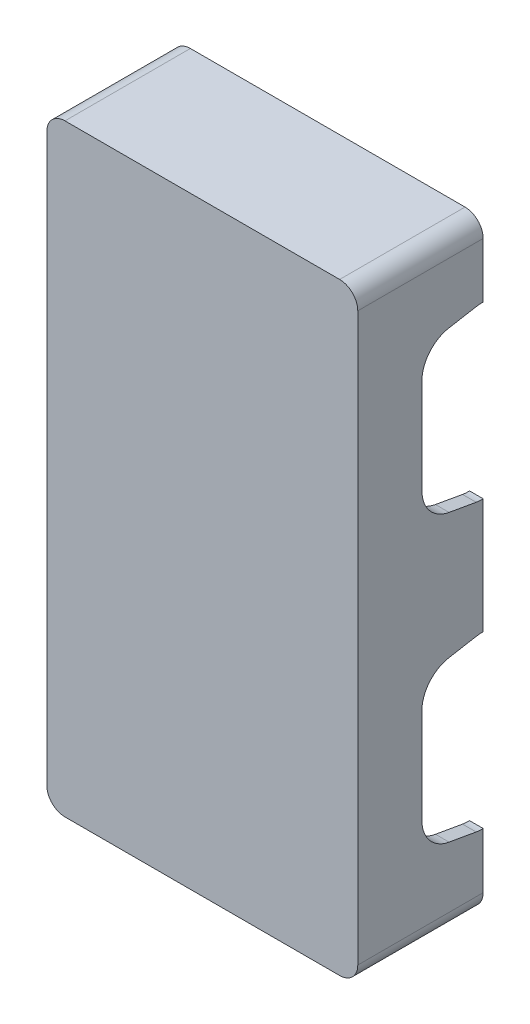
SolidWorks part; units mm, degrees
ref_plane "Front Plane" through (0, 0, 0) normal (0, 0, 1) x (1, 0, 0)
ref_plane "Top Plane" through (0, 0, 0) normal (0, 1, 0) x (1, 0, 0)
ref_plane "Right Plane" through (0, 0, 0) normal (1, 0, 0) x (0, 0, -1)
sketch "Sketch1" plane through (0, 0, 0) normal (0, 0, 1) x (1, 0, 0)
  line L0 (-32.3, 64.5) -> (2, 64.5)
  line L1 (-30.3, 62.5) -> (0, 62.5) construction
  line L2 (-30.3, 62.5) -> (-30.3, 0) construction
  line L3 (-30.3, 0) -> (0, 0) construction
  line L4 (0, 62.5) -> (0, 0) construction
  line L5 (2, 64.5) -> (2, -2)
  line L6 (-32.3, -2) -> (2, -2)
  line L7 (-32.3, 64.5) -> (-32.3, -2)
  dimension "D1" = 2
extrude "Boss-Extrude3" add sketch "Sketch1" along normal offset from surface 1.5 and the other way offset from surface (16.5814 mm away) 1.5
sketch "Sketch3" plane through (-32.3, 0, 0) normal (-1, 0, 0) x (0, 0, 1)
  line L0 (-13.4464, 47.86) -> (-13.4464, 14.26) construction
  line L1 (-9.7847, 11.1874) -> (-6.7947, 11.7146) construction
  line L2 (-4.2164, 14.7872) -> (-4.2164, 47.3328) construction
  line L3 (-6.7947, 50.4054) -> (-9.7847, 50.9326) construction
  line L5 (-13.9464, 47.86) -> (-13.9464, 14.26)
  line L6 (-9.6978, 10.695) -> (-6.7078, 11.2222)
  line L12 (-13.4464, 47.86) -> (-13.4464, 14.26) construction
  line L13 (-9.7847, 11.1874) -> (-6.7947, 11.7146) construction
  line L14 (-4.2164, 14.7872) -> (-4.2164, 47.3328) construction
  line L15 (-6.7947, 50.4054) -> (-9.7847, 50.9326) construction
  line L16 (-3.7164, 14.7872) -> (-3.7164, 47.3328)
  line L17 (-6.7078, 50.8978) -> (-9.6978, 51.425)
  spline S0 degree 3 poles (-13.4464, 14.26) (-13.4464, 12.1686) (-11.8443, 10.8242) (-9.7847, 11.1874) knots 0 0 0 0 1 1 1 1 weights 1 0.761858 0.761858 1 construction
  spline S1 degree 3 poles (-6.7947, 11.7146) (-5.2347, 11.9897) (-4.2164, 13.2032) (-4.2164, 14.7872) knots 0 0 0 0 1 1 1 1 weights 1 0.84403 0.84403 1 construction
  spline S2 degree 3 poles (-4.2164, 47.3328) (-4.2164, 48.9169) (-5.2347, 50.1303) (-6.7947, 50.4054) knots 0 0 0 0 1 1 1 1 weights 1 0.84403 0.84403 1 construction
  spline S3 degree 3 poles (-9.7847, 50.9326) (-11.8443, 51.2958) (-13.4464, 49.9514) (-13.4464, 47.86) knots 0 0 0 0 1 1 1 1 weights 1 0.761858 0.761858 1 construction
  spline S4 degree 3 poles (-13.4464, 14.26) (-13.4464, 12.1686) (-11.8443, 10.8242) (-9.7847, 11.1874) knots 0 0 0 0 1 1 1 1 weights 1 0.761858 0.761858 1 construction
  spline S5 degree 3 poles (-6.7947, 11.7146) (-5.2347, 11.9897) (-4.2164, 13.2032) (-4.2164, 14.7872) knots 0 0 0 0 1 1 1 1 weights 1 0.84403 0.84403 1 construction
  spline S6 degree 3 poles (-4.2164, 47.3328) (-4.2164, 48.9169) (-5.2347, 50.1303) (-6.7947, 50.4054) knots 0 0 0 0 1 1 1 1 weights 1 0.84403 0.84403 1 construction
  spline S7 degree 3 poles (-9.7847, 50.9326) (-11.8443, 51.2958) (-13.4464, 49.9514) (-13.4464, 47.86) knots 0 0 0 0 1 1 1 1 weights 1 0.761858 0.761858 1 construction
  spline S8 degree 1 poles (-13.9464, 14.26) (-9.6978, 10.695) knots 0 0 1 1 construction
  spline S9 degree 1 poles (-6.7078, 11.2222) (-3.7164, 14.7872) knots 0 0 1 1 construction
  spline S10 degree 1 poles (-3.7164, 47.3328) (-6.7078, 50.8978) knots 0 0 1 1 construction
  spline S11 degree 1 poles (-9.6978, 51.425) (-13.9464, 47.86) knots 0 0 1 1 construction
  spline S12 degree 3 poles (-13.9464, 14.26) (-13.9464, 14.0193) (-13.9017, 13.5499) (-13.5942, 12.5442) (-12.7412, 11.3822) (-11.4487, 10.7439) (-10.4049, 10.6158) (-9.9349, 10.6532) (-9.6978, 10.695) knots 0 0 0 0 0.125 0.25 0.5 0.75 0.875 1 1 1 1
  spline S13 degree 3 poles (-6.7078, 11.2222) (-6.308, 11.2927) (-5.5445, 11.5574) (-4.4978, 12.4053) (-3.8445, 13.5834) (-3.7164, 14.3812) (-3.7164, 14.7872) knots 0 0 0 0 0.25 0.5 0.75 1 1 1 1
  spline S14 degree 3 poles (-3.7164, 47.3328) (-3.7164, 47.7388) (-3.8445, 48.5366) (-4.4978, 49.7147) (-5.5445, 50.5626) (-6.308, 50.8273) (-6.7078, 50.8978) knots 0 0 0 0 0.25 0.5 0.75 1 1 1 1
  spline S15 degree 3 poles (-9.6978, 51.425) (-9.9349, 51.4668) (-10.4049, 51.5042) (-11.4487, 51.3761) (-12.7412, 50.7379) (-13.5942, 49.5758) (-13.9017, 48.5701) (-13.9464, 48.1007) (-13.9464, 47.86) knots 0 0 0 0 0.125 0.25 0.5 0.75 0.875 1 1 1 1
  dimension "D1" = 0.5
extrude "Cut-Extrude1" cut sketch "Sketch3" against normal blind 5
sketch "Sketch4" plane through (2, 0, 0) normal (1, 0, 0) x (0, 0, -1)
  line L0 (6.9047, 38.7046) -> (9.8947, 38.1774) construction
  line L1 (4.3264, 52.2728) -> (4.3264, 41.7772) construction
  line L2 (13.5564, 41.25) -> (13.5564, 52.8) construction
  line L3 (9.8947, 55.8726) -> (6.9047, 55.3454) construction
  line L4 (6.9047, 38.7046) -> (9.8947, 38.1774) construction
  line L5 (4.3264, 52.2728) -> (4.3264, 41.7772) construction
  line L6 (13.5564, 41.25) -> (13.5564, 52.8) construction
  line L7 (9.8947, 55.8726) -> (6.9047, 55.3454) construction
  line L8 (4.3264, 20.7728) -> (4.3264, 10.2772) construction
  line L9 (6.9047, 7.2046) -> (9.8947, 6.6774) construction
  line L10 (13.5564, 9.75) -> (13.5564, 21.3) construction
  line L11 (9.8947, 24.3726) -> (6.9047, 23.8454) construction
  line L12 (4.3264, 20.7728) -> (4.3264, 10.2772) construction
  line L13 (6.9047, 7.2046) -> (9.8947, 6.6774) construction
  line L14 (13.5564, 9.75) -> (13.5564, 21.3) construction
  line L15 (9.8947, 24.3726) -> (6.9047, 23.8454) construction
  line L16 (6.8178, 38.2122) -> (9.8078, 37.685)
  line L17 (14.0564, 41.25) -> (14.0564, 52.8)
  line L18 (9.8078, 56.365) -> (6.8178, 55.8378)
  line L19 (3.8264, 52.2728) -> (3.8264, 41.7772)
  line L20 (3.8264, 20.7728) -> (3.8264, 10.2772)
  line L21 (6.8178, 6.7122) -> (9.8078, 6.185)
  line L22 (14.0564, 9.75) -> (14.0564, 21.3)
  line L23 (9.8078, 24.865) -> (6.8178, 24.3378)
  spline S0 degree 3 poles (4.3264, 41.7772) (4.3264, 40.1932) (5.3447, 38.9797) (6.9047, 38.7046) knots 0 0 0 0 1 1 1 1 weights 1 0.84403 0.84403 1 construction
  spline S1 degree 3 poles (9.8947, 38.1774) (11.9543, 37.8142) (13.5564, 39.1586) (13.5564, 41.25) knots 0 0 0 0 1 1 1 1 weights 1 0.761858 0.761858 1 construction
  spline S2 degree 3 poles (6.9047, 55.3454) (5.3447, 55.0703) (4.3264, 53.8568) (4.3264, 52.2728) knots 0 0 0 0 1 1 1 1 weights 1 0.84403 0.84403 1 construction
  spline S3 degree 3 poles (13.5564, 52.8) (13.5564, 54.8914) (11.9543, 56.2358) (9.8947, 55.8726) knots 0 0 0 0 1 1 1 1 weights 1 0.761858 0.761858 1 construction
  spline S4 degree 3 poles (4.3264, 41.7772) (4.3264, 40.1932) (5.3447, 38.9797) (6.9047, 38.7046) knots 0 0 0 0 1 1 1 1 weights 1 0.84403 0.84403 1 construction
  spline S5 degree 3 poles (9.8947, 38.1774) (11.9543, 37.8142) (13.5564, 39.1586) (13.5564, 41.25) knots 0 0 0 0 1 1 1 1 weights 1 0.761858 0.761858 1 construction
  spline S6 degree 3 poles (6.9047, 55.3454) (5.3447, 55.0703) (4.3264, 53.8568) (4.3264, 52.2728) knots 0 0 0 0 1 1 1 1 weights 1 0.84403 0.84403 1 construction
  spline S7 degree 3 poles (13.5564, 52.8) (13.5564, 54.8914) (11.9543, 56.2358) (9.8947, 55.8726) knots 0 0 0 0 1 1 1 1 weights 1 0.761858 0.761858 1 construction
  spline S8 degree 3 poles (4.3264, 10.2772) (4.3264, 8.6932) (5.3447, 7.4797) (6.9047, 7.2046) knots 0 0 0 0 1 1 1 1 weights 1 0.84403 0.84403 1 construction
  spline S9 degree 3 poles (9.8947, 6.6774) (11.9543, 6.3142) (13.5564, 7.6586) (13.5564, 9.75) knots 0 0 0 0 1 1 1 1 weights 1 0.761858 0.761858 1 construction
  spline S10 degree 3 poles (6.9047, 23.8454) (5.3447, 23.5703) (4.3264, 22.3568) (4.3264, 20.7728) knots 0 0 0 0 1 1 1 1 weights 1 0.84403 0.84403 1 construction
  spline S11 degree 3 poles (13.5564, 21.3) (13.5564, 23.3914) (11.9543, 24.7358) (9.8947, 24.3726) knots 0 0 0 0 1 1 1 1 weights 1 0.761858 0.761858 1 construction
  spline S12 degree 3 poles (4.3264, 10.2772) (4.3264, 8.6932) (5.3447, 7.4797) (6.9047, 7.2046) knots 0 0 0 0 1 1 1 1 weights 1 0.84403 0.84403 1 construction
  spline S13 degree 3 poles (9.8947, 6.6774) (11.9543, 6.3142) (13.5564, 7.6586) (13.5564, 9.75) knots 0 0 0 0 1 1 1 1 weights 1 0.761858 0.761858 1 construction
  spline S14 degree 3 poles (6.9047, 23.8454) (5.3447, 23.5703) (4.3264, 22.3568) (4.3264, 20.7728) knots 0 0 0 0 1 1 1 1 weights 1 0.84403 0.84403 1 construction
  spline S15 degree 3 poles (13.5564, 21.3) (13.5564, 23.3914) (11.9543, 24.7358) (9.8947, 24.3726) knots 0 0 0 0 1 1 1 1 weights 1 0.761858 0.761858 1 construction
  spline S16 degree 1 poles (9.8078, 37.685) (14.0564, 41.25) knots 0 0 1 1 construction
  spline S17 degree 1 poles (14.0564, 52.8) (9.8078, 56.365) knots 0 0 1 1 construction
  spline S18 degree 1 poles (6.8178, 55.8378) (3.8264, 52.2728) knots 0 0 1 1 construction
  spline S19 degree 1 poles (3.8264, 41.7772) (6.8178, 38.2122) knots 0 0 1 1 construction
  spline S20 degree 3 poles (9.8078, 37.685) (10.0449, 37.6432) (10.5149, 37.6058) (11.5587, 37.7339) (12.8512, 38.3721) (13.7042, 39.5342) (14.0117, 40.5399) (14.0564, 41.0093) (14.0564, 41.25) knots 0 0 0 0 0.125 0.25 0.5 0.75 0.875 1 1 1 1
  spline S21 degree 3 poles (14.0564, 52.8) (14.0564, 53.0407) (14.0117, 53.5101) (13.7042, 54.5158) (12.8512, 55.6778) (11.5587, 56.3161) (10.5149, 56.4442) (10.0449, 56.4068) (9.8078, 56.365) knots 0 0 0 0 0.125 0.25 0.5 0.75 0.875 1 1 1 1
  spline S22 degree 3 poles (6.8178, 55.8378) (6.418, 55.7673) (5.6545, 55.5026) (4.6078, 54.6547) (3.9545, 53.4766) (3.8264, 52.6788) (3.8264, 52.2728) knots 0 0 0 0 0.25 0.5 0.75 1 1 1 1
  spline S23 degree 3 poles (3.8264, 41.7772) (3.8264, 41.3712) (3.9545, 40.5734) (4.6078, 39.3953) (5.6545, 38.5474) (6.418, 38.2827) (6.8178, 38.2122) knots 0 0 0 0 0.25 0.5 0.75 1 1 1 1
  spline S24 degree 1 poles (3.8264, 10.2772) (6.8178, 6.7122) knots 0 0 1 1 construction
  spline S25 degree 1 poles (9.8078, 6.185) (14.0564, 9.75) knots 0 0 1 1 construction
  spline S26 degree 1 poles (14.0564, 21.3) (9.8078, 24.865) knots 0 0 1 1 construction
  spline S27 degree 1 poles (6.8178, 24.3378) (3.8264, 20.7728) knots 0 0 1 1 construction
  spline S28 degree 3 poles (3.8264, 10.2772) (3.8264, 9.8712) (3.9545, 9.0734) (4.6078, 7.8953) (5.6545, 7.0474) (6.418, 6.7827) (6.8178, 6.7122) knots 0 0 0 0 0.25 0.5 0.75 1 1 1 1
  spline S29 degree 3 poles (9.8078, 6.185) (10.0449, 6.1432) (10.5149, 6.1058) (11.5587, 6.2339) (12.8512, 6.8722) (13.7042, 8.0342) (14.0117, 9.0399) (14.0564, 9.5093) (14.0564, 9.75) knots 0 0 0 0 0.125 0.25 0.5 0.75 0.875 1 1 1 1
  spline S30 degree 3 poles (14.0564, 21.3) (14.0564, 21.5407) (14.0117, 22.0101) (13.7042, 23.0158) (12.8512, 24.1779) (11.5587, 24.8161) (10.5149, 24.9442) (10.0449, 24.9068) (9.8078, 24.865) knots 0 0 0 0 0.125 0.25 0.5 0.75 0.875 1 1 1 1
  spline S31 degree 3 poles (6.8178, 24.3378) (6.418, 24.2673) (5.6545, 24.0026) (4.6078, 23.1547) (3.9545, 21.9766) (3.8264, 21.1788) (3.8264, 20.7728) knots 0 0 0 0 0.25 0.5 0.75 1 1 1 1
  dimension "D1" = 0.5
extrude "Cut-Extrude2" cut sketch "Sketch4" against normal blind 5
fillet "Fillet1" radius 2 4 edges at (2, -2, -6.6657) (-32.3, -2, -6.6657) (-32.3, 64.5, -6.6657) (2, 64.5, -6.6657)
sketch "Sketch5" plane through (0, 0, -16.5814) normal (0, 0, -1) x (-1, 0, 0)
  line L1 (-13.3819, 71.2406) -> (41.749, 71.2406)
  line L2 (-13.3819, 71.2406) -> (-13.3819, -6.0591)
  line L3 (-13.3819, -6.0591) -> (41.749, -6.0591)
  line L4 (41.749, 71.2406) -> (41.749, -6.0591)
extrude "Cut-Extrude3" cut sketch "Sketch5" against normal blind 6
sketch "Sketch6" plane through (0, 0, -10.5814) normal (0, 0, -1) x (-1, 0, 0)
  line L0 (30.3, 64.5) -> (0, 64.5) construction
  line L1 (-0.5, 63) -> (30.8, 63)
  line L2 (-0.5, 63) -> (-0.5, -0.5)
  line L3 (-0.5, -0.5) -> (30.8, -0.5)
  line L4 (30.8, 63) -> (30.8, -0.5)
  line L5 (32.3, 51.4708) -> (32.3, 62.5) construction
  line L6 (-2, 62.5) -> (-2, 56.417) construction
  line L7 (0, -2) -> (30.3, -2) construction
  dimension "D1" = 1.5
  dimension "D2" = 1.5
  dimension "D3" = 1.5
  dimension "D4" = 1.5
extrude "Cut-Extrude4" cut sketch "Sketch6" against normal offset from surface (12.5814 mm away) 1.25 up to face at (-15.15, 31.25, 3.25)
sketch "Sketch7" plane through (0, 0, 2) normal (0, 0, -1) x (-1, 0, 0)
  line L0 (1, 61.5) -> (1, 1)
  line L1 (-0.5, 63) -> (30.8, 63)
  line L2 (-0.5, 63) -> (-0.5, -0.5)
  line L3 (-0.5, -0.5) -> (30.8, -0.5)
  line L4 (30.8, 63) -> (30.8, -0.5)
  line L5 (1, 1) -> (29.3, 1)
  line L6 (29.3, 61.5) -> (29.3, 1)
  line L7 (1, 61.5) -> (29.3, 61.5)
  dimension "D1" = 1.5
extrude "Boss-Extrude4" add sketch "Sketch7" along normal blind 1.5
fillet "Fillet2" radius 1 4 edges at (-1, 1, 1.25) (-29.3, 1, 1.25) (-29.3, 61.5, 1.25) (-1, 61.5, 1.25)
fillet "Fillet3" radius 0.3 8 edges at (-29.0071, 61.2071, 2) (-29.3, 31.25, 2) (-29.0071, 1.2929, 2) (-15.15, 1, 2) (-1.2929, 1.2929, 2) (-1, 31.25, 2) (-1.2929, 61.2071, 2) (-15.15, 61.5, 2)
fillet "Fillet4" radius 0.3 4 edges at (0.5, -0.5, -5.0407) (-30.8, -0.5, -5.0407) (-30.8, 63, -5.0407) (0.5, 63, -5.0407)
sketch "Sketch8" plane through (-32.3, 0, 0) normal (-1, 0, 0) x (0, 0, 1)
  line L2 (-11.8605, 54.5097) -> (-11.8605, 7.5529)
  line L4 (-5.8605, 54.5097) -> (-5.8605, 7.5529)
  arc A0 (-5.8605, 54.5097) -> (-11.8605, 54.5097) centre (-8.8605, 54.5097) ccw
  arc A1 (-11.8605, 7.5529) -> (-5.8605, 7.5529) centre (-8.8605, 7.5529) ccw
extrude "Cut-Extrude5" cut sketch "Sketch8" against normal up to surface (1.5 mm away) up to face at (-30.8, 31.1378, -6.6895)
